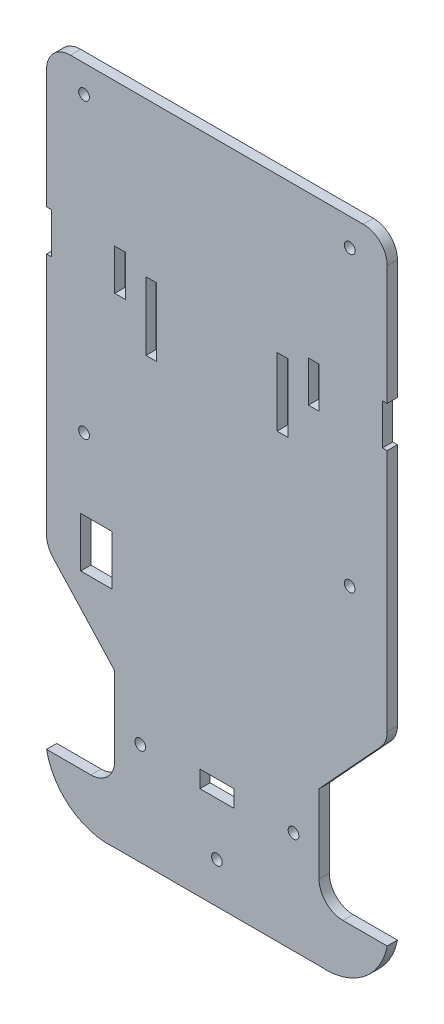
SolidWorks part; units mm, degrees
ref_plane "Front Plane" through (0, 0, 0) normal (0, 0, 1) x (1, 0, 0)
ref_plane "Top Plane" through (0, 0, 0) normal (0, 1, 0) x (1, 0, 0)
ref_plane "Right Plane" through (0, 0, 0) normal (1, 0, 0) x (0, 0, -1)
sketch "Sketch1" plane through (0, 0, 0) normal (0, 0, 1) x (1, 0, 0)
  line L0 (0, -39) -> (0, 56) construction
  line L1 (50, 56) -> (-50, 56) construction
  line L7 (30, -39) -> (-30, -39)
  line L20 (-30, -9) -> (30, -9) construction
  line L27 (-30, 113.9439) -> (-26.85, 113.9439)
  line L28 (-30, 113.9439) -> (-30, 101.9439)
  line L29 (-30, 101.9439) -> (-26.85, 101.9439)
  line L30 (-26.85, 113.9439) -> (-26.85, 101.9439)
  line L38 (0, 155) -> (0, 56) construction
  line L40 (-39.3, 158.5) -> (-39.3, 114.3546) construction
  line L41 (-50, 56) -> (50, 56)
  line L42 (-50, 56) -> (-50, 156)
  line L43 (-50, 156) -> (50, 156)
  line L44 (50, 56) -> (50, 156)
  line L45 (-39.33, 96.9439) -> (-30, 96.9439) construction
  line L46 (-51.75, 113.9439) -> (-51.75, 101.9439)
  line L47 (-48.6, 101.9439) -> (-51.75, 101.9439)
  line L48 (-48.6, 113.9439) -> (-48.6, 101.9439)
  line L49 (-48.6, 113.9439) -> (-51.75, 113.9439)
  line L50 (39.3, 158.5) -> (39.3, 114.3546) construction
  line L51 (48.6, 113.9439) -> (51.75, 113.9439)
  line L52 (48.6, 113.9439) -> (48.6, 101.9439)
  line L53 (48.6, 101.9439) -> (51.75, 101.9439)
  line L54 (51.75, 113.9439) -> (51.75, 101.9439)
  line L55 (50, 56) -> (50, 156)
  line L56 (26.85, 113.9439) -> (26.85, 101.9439)
  line L57 (30, 101.9439) -> (26.85, 101.9439)
  line L58 (30, 113.9439) -> (30, 101.9439)
  line L59 (30, 113.9439) -> (26.85, 113.9439)
  line L60 (-50, -24) -> (50, -24)
  line L61 (-30, 6) -> (30, 6)
  line L62 (30, 6) -> (30, -24)
  line L63 (30, -24) -> (-30, -24)
  line L64 (-30, -24) -> (-30, 6)
  line L72 (-40, 41) -> (-30.8, 41)
  line L73 (-40, 41) -> (-40, 26.35)
  line L74 (-40, 26.35) -> (-30.8, 26.35)
  line L75 (-30.8, 41) -> (-30.8, 26.35)
  line L76 (-5, -6.5) -> (5, -6.5)
  line L77 (-50, 27.7301) -> (-30, 6)
  line L78 (50, 27.7301) -> (-50, 27.7301)
  line L79 (50, 27.7301) -> (50, 56)
  line L80 (50, 56) -> (-50, 56)
  line L81 (-50, 27.7301) -> (-50, 56)
  line L82 (50, 27.7301) -> (30, 6)
  line L83 (-5, -6.5) -> (-5, -11.5)
  line L84 (-5, -11.5) -> (5, -11.5)
  line L85 (5, -6.5) -> (5, -11.5)
  line L86 (-5, -6.5) -> (5, -11.5) construction
  line L87 (-5, -11.5) -> (5, -6.5) construction
  line L92 (-50, 55) -> (-36, 55) construction
  line L94 (17.6715, 45.5) -> (17.6715, 156) construction
  line L95 (20.8215, 110.75) -> (17.6715, 110.75)
  line L96 (20.8215, 110.75) -> (20.8215, 90.75)
  line L97 (20.8215, 90.75) -> (17.6715, 90.75)
  line L99 (17.6715, 110.75) -> (17.6715, 90.75)
  line L100 (-17.6715, 110.75) -> (-17.6715, 90.75)
  line L101 (-20.8215, 90.75) -> (-17.6715, 90.75)
  line L102 (-20.8215, 110.75) -> (-20.8215, 90.75)
  line L103 (-20.8215, 110.75) -> (-17.6715, 110.75)
  circle A2 centre (0, -27) radius 1.575
  circle A3 centre (-22.5, -9) radius 1.575
  circle A4 centre (22.5, -9) radius 1.575
  circle A13 centre (-39, 62) radius 1.575
  arc A18 (-50, -24) -> (-30, -39) centre (-31.7935, -20.558) ccw
  arc A19 (30, -39) -> (50, -24) centre (31.7935, -20.558) ccw
  circle A20 centre (-39, 148) radius 1.575
  circle A21 centre (39, 148) radius 1.575
  circle A22 centre (39, 62) radius 1.575
  point P5 (0, 156)
  point P7 (0, -39)
  point P42 (17.6715, 100.75)
  point P44 (20.8215, 100.75)
  point P79 (30, -9)
  point P87 (0, -9)
  point P96 (0, -24)
  dimension "D6" = 3.15
  dimension "D7" = 3.15
  dimension "D11" = 7
  dimension "D14" = 20
  dimension "D15" = 3.15
  dimension "D23" = 3.15
  dimension "D24" = 3.15
  dimension "D25" = 11
  dimension "D26" = 11
  dimension "D28" = 6
  dimension "D21" = 3.15
  dimension "D3" = 60
  dimension "D4" = 30
  dimension "D5" = 50
  dimension "D8" = 100
  dimension "D9" = 15
  dimension "D10" = 3
  dimension "D17" = 5
  dimension "D18" = 12
  dimension "D19" = 100
  dimension "D20" = 100
  dimension "D22" = 8
  dimension "D27" = 20
  dimension "875" = 9.3
  dimension "D32" = 14.65
  dimension "D33" = 9.2
  dimension "15" = 15
  dimension "D35" = 10
  dimension "12" = 10
  dimension "D36" = 5
  dimension "D37" = 15
extrude "Boss-Extrude2" add sketch "Sketch1" along normal blind 3 contours L43 | L7 A19 L60 A18 A2 | L60 L62 L61 L64 L76 L85 L84 L83 A3 A4 | L82 L78 L77 L61 | L81 L78 L79 L41 L72 L75 L74 L73 | L53 L52 L51 L44 L43 L42 L49 L48 L47 L41 A21 A20 A13 L59 L58 L57 L56 L27 L30 L29 L28 A22 region at (0, -31.1664, 0) region at (0, -23.3292, 0) region at (0.2604, 17.7023, 0) region at (1.5977, 42.2035, 0) region at (0, 106.0494, 0)
fillet "Fillet1" radius 7 8 edges at (-30, -39, 1.5) (30, -39, 1.5) (-50, 156, 1.5) (50, 156, 1.5) (30, -24, 1.5) (-30, -24, 1.5) (50, 27.7301, 1.5) (-50, 27.7301, 1.5)
